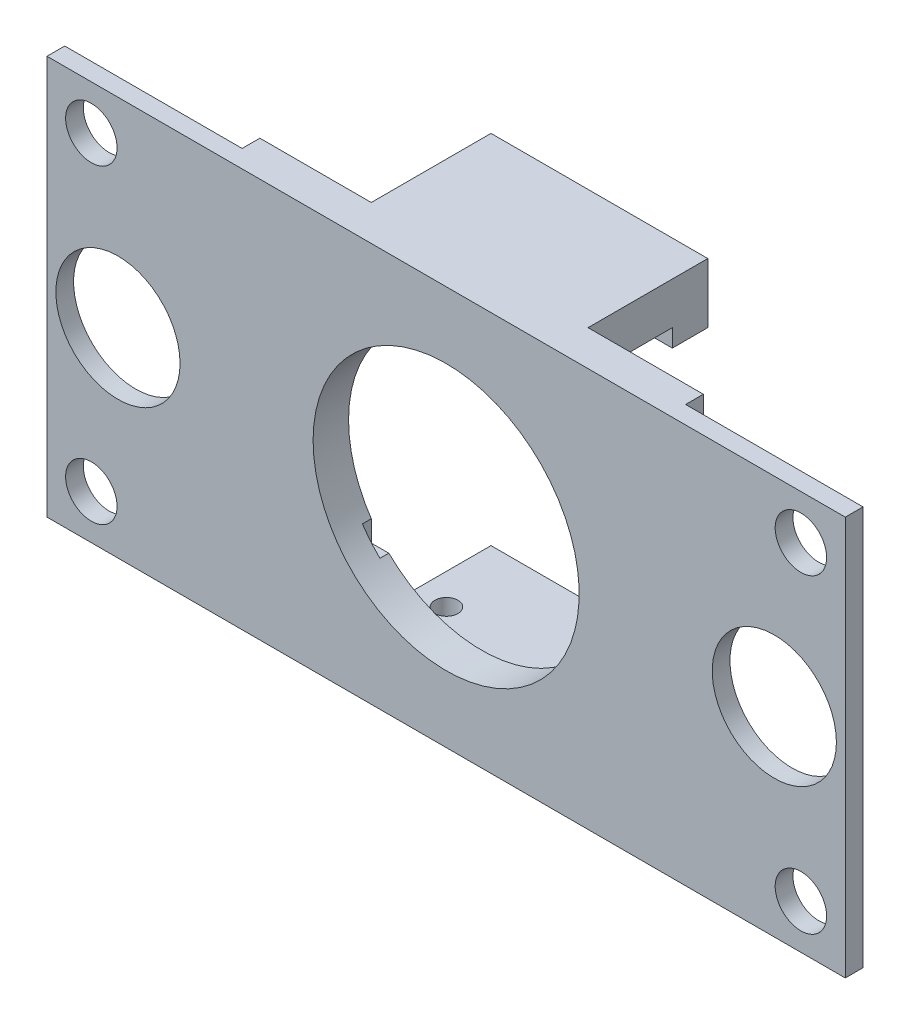
SolidWorks part; units mm, degrees
ref_plane "Front" through (0, 0, 0) normal (0, 0, 1) x (1, 0, 0)
ref_plane "Top" through (0, 0, 0) normal (0, 1, 0) x (1, 0, 0)
ref_plane "Right" through (0, 0, 0) normal (1, 0, 0) x (0, 0, -1)
sketch "草图1" plane through (0, 0, 0) normal (0, 0, 1) x (1, 0, 0)
  line L1 (-45, 22.5) -> (45, 22.5)
  line L2 (-45, 22.5) -> (-45, -22.5)
  line L3 (-45, -22.5) -> (45, -22.5)
  line L4 (45, 22.5) -> (45, -22.5)
  circle A0 centre (-40, 17.5) radius 2.9
  circle A1 centre (-40, -17.5) radius 2.9
  circle A2 centre (40, 17.5) radius 2.9
  circle A3 centre (40, -17.5) radius 2.9
  circle A7 centre (-37, 0) radius 7
  circle A8 centre (37, 0) radius 7
  point P0 (0, 0)
  point P10 (0, 0)
  point P15 (0, 0)
extrude "凸台-拉伸2" add sketch "草图1" against normal blind 2
sketch "草图2" plane through (0, 0, -2) normal (0, 0, -1) x (-1, 0, 0)
  line L0 (0, -22.5) -> (-25, -22.5)
  line L1 (45, -22.5) -> (-45, -22.5) construction
  line L2 (-25, -22.5) -> (-25, 22.5)
  line L3 (-45, 22.5) -> (45, 22.5) construction
  line L4 (-25, 22.5) -> (25, 22.5)
  line L5 (25, 22.5) -> (25, -22.5)
  line L6 (25, -22.5) -> (0, -22.5)
extrude "凸台-拉伸3" add sketch "草图2" along normal blind 2
sketch "草图3" plane through (0, 0, -4) normal (0, 0, -1) x (-1, 0, 0)
  circle A0 centre (0, 0) radius 15
extrude "切除-拉伸1" cut sketch "草图3" against normal through all
sketch "草图4" plane through (0, 0, -4) normal (0, 0, -1) x (-1, 0, 0)
  line L2 (0, -22.5) -> (-12, -22.5)
  line L3 (-25, -22.5) -> (25, -22.5) construction
  line L4 (-12, -22.5) -> (-12, -17.75)
  line L5 (-12, -17.75) -> (-12, -10.75)
  line L6 (-12, -10.75) -> (-12, 2.25)
  line L7 (-12, 2.25) -> (12.4412, 2.25)
  line L8 (12.4412, 2.25) -> (12.4412, -22.5)
  line L9 (12.4412, -22.5) -> (0, -22.5)
  line L10 (-12, -10.75) -> (12.4412, -10.75)
  line L11 (-12, -17.75) -> (12.4412, -17.75)
  line L12 (12.4412, -17.75) -> (12.4412, 17.75) construction
  line L13 (12.4412, 17.75) -> (12.4412, 22.5)
  line L14 (25, 22.5) -> (-25, 22.5) construction
  line L15 (12.4412, 22.5) -> (-12, 22.5)
  line L16 (-12, 22.5) -> (-12, 17.75)
  line L17 (-12, 17.75) -> (12.4412, 17.75)
  circle M3 centre (0, 0) radius 15
  line M4 (-25, -22.5) -> (25, -22.5)
  line M6 (25, 22.5) -> (-25, 22.5)
extrude "切除-拉伸2" cut sketch "草图4" against normal blind 1 contours L10 L8 M3 | L6 L10 M3 | L10 L8 L7 L6 M3 region at (11.5005, -10.1821, -4) region at (-11.8042, -9.988, -4) region at (-0.1878, -4.1861, -4)
extrude "凸台-拉伸4" add sketch "草图4<3>" along normal blind 13.5 contours L11 L4 L8 M4 region at (-0.2206, -20.125, -4)
sketch "草图4<3>" plane through (0, 0, -4) normal (0, 0, -1) x (-1, 0, 0) same geometry as "草图4"
sketch "草图5" plane through (0, -17.75, 0) normal (0, 1, 0) x (1, 0, 0)
  line L0 (-0.2206, 4) -> (-0.2206, 9)
  line L1 (12, 4) -> (-12.4412, 4) construction
  line L2 (-0.2206, 9) -> (8.5294, 9) construction
  line L3 (-0.2206, 9) -> (-8.9706, 9) construction
  circle A0 centre (-8.9706, 9) radius 1.3
  circle A1 centre (8.5294, 9) radius 1.3
extrude "切除-拉伸3" cut sketch "草图5" against normal through all contours A0 | A1 region at (-8.9706, -17.75, -9) region at (8.5294, -17.75, -9)
extrude "凸台-拉伸5" add sketch "草图4<4>" along normal blind 13.5 contours L16 L17 L13 M6 region at (-0.2206, 20.125, -4)
sketch "草图4<4>" plane through (0, 0, -4) normal (0, 0, -1) x (-1, 0, 0) same geometry as "草图4"
sketch "草图6" plane through (0, 17.75, 0) normal (0, -1, 0) x (1, 0, 0)
  line L0 (-12.4412, -4) -> (-12.4412, -13.5) construction
  line L1 (-12.4412, -17.5) -> (-12.4412, -4) construction
  line L2 (-12.4412, -13.5) -> (12, -13.5)
  line L3 (12, -17.5) -> (12, -4) construction
  line L4 (12, -13.5) -> (12, -17.5)
  line L5 (12, -17.5) -> (-12.4412, -17.5)
  line L6 (-12.4412, -17.5) -> (-12.4412, -13.5)
extrude "凸台-拉伸6" add sketch "草图6" along normal blind 2
